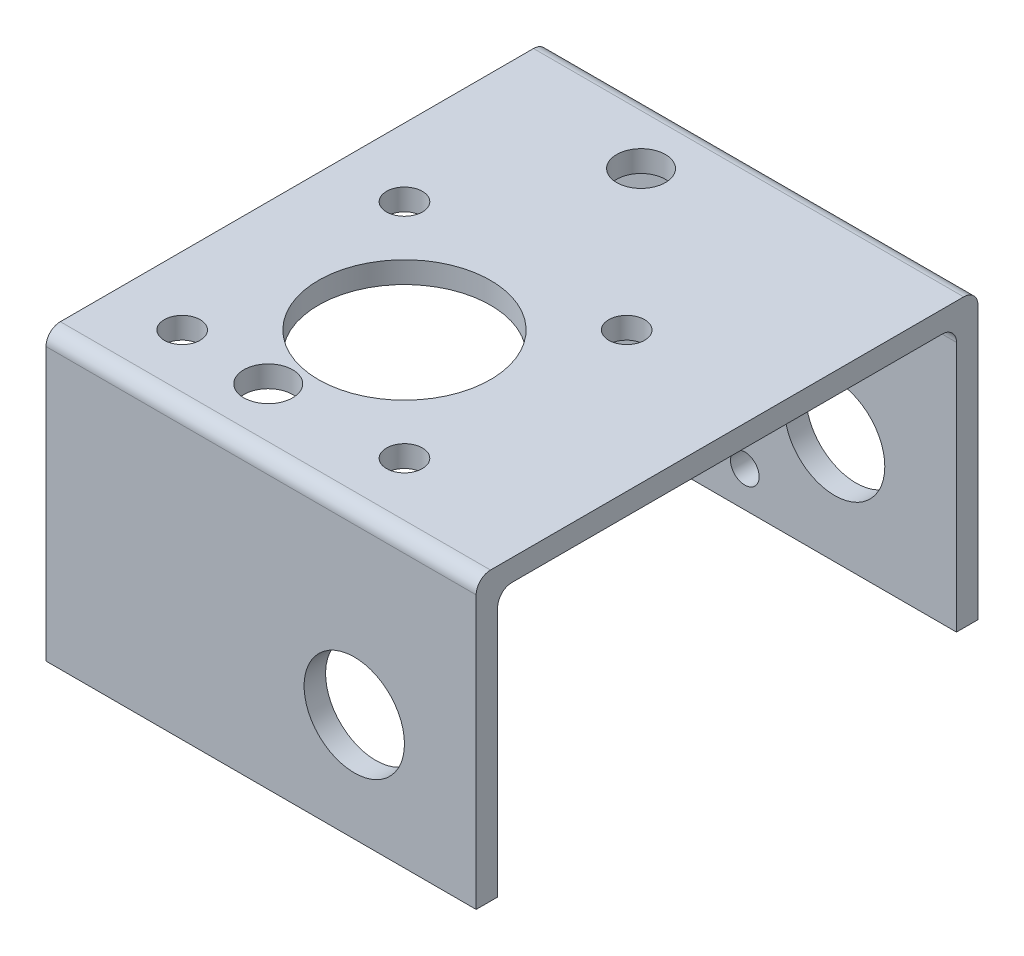
SolidWorks part; units mm, degrees
material "6061 合金"
ref_plane "前视基准面" through (0, 0, 0) normal (0, 0, 1) x (1, 0, 0)
ref_plane "上视基准面" through (0, 0, 0) normal (0, 1, 0) x (1, 0, 0)
ref_plane "右视基准面" through (0, 0, 0) normal (1, 0, 0) x (0, 0, -1)
sketch "草图1" plane through (0, 0, 0) normal (1, 0, 0) x (0, 0, -1)
  line L0 (0, 0) -> (3, 0)
  line L1 (3, 0) -> (3, 35)
  line L2 (5, 37) -> (65, 37)
  line L3 (67, 35) -> (67, 0)
  line L4 (67, 0) -> (70, 0)
  line L5 (70, 0) -> (70, 38)
  line L6 (68, 40) -> (2, 40)
  line L7 (0, 38) -> (0, 0)
  arc A0 (70, 38) -> (68, 40) centre (68, 38) ccw
  arc A1 (65, 37) -> (67, 35) centre (65, 35) cw
  arc A2 (3, 35) -> (5, 37) centre (5, 35) cw
  arc A3 (2, 40) -> (0, 38) centre (2, 38) ccw
  point P11 (70, 40)
  point P18 (0, 40)
  dimension "D6" = 2
  dimension "D1" = 3
  dimension "D2" = 3
  dimension "D3" = 3
  dimension "D4" = 70
  dimension "D5" = 40
extrude "凸台-拉伸1" add sketch "草图1" along normal blind 60
sketch "草图2" plane through (0, 40, 0) normal (0, 1, 0) x (1, 0, 0)
  line L0 (25, -19.2967) -> (25, 88.9945) construction
  line L1 (-21.8978, 25) -> (76.0197, 25) construction
  line L2 (60, 0) -> (0, 0) construction
  line L3 (0, 68) -> (0, 2) construction
  line L4 (-9.4226, 9.5) -> (65.353, 9.5) construction
  line L5 (9.5, -18.3438) -> (9.5, 73.6232) construction
  circle A0 centre (9.5, 9.5) radius 2.5
  circle A1 centre (40.5, 9.5) radius 2.5
  circle A2 centre (40.5, 40.5) radius 2.5
  circle A3 centre (9.5, 40.5) radius 2.5
  circle A4 centre (25, 25) radius 12
  dimension "D5" = 5
  dimension "D8" = 24
  dimension "D1" = 25
  dimension "D2" = 25
  dimension "D3" = 15.5
  dimension "D4" = 15.5
  dimension "D6" = 2
  dimension "D7" = 2
extrude "切除-拉伸1" cut sketch "草图2" against normal up to next
sketch "草图3" plane through (0, 0, 0) normal (0, 0, 1) x (1, 0, 0)
  line L0 (25, -15.1885) -> (25, 47.9229) construction
  line L1 (0, 38) -> (0, 0) construction
  line L2 (60, 40) -> (0, 40) construction
  circle A0 centre (43, 15) radius 7
  dimension "D1" = 14
  dimension "D2" = 25
  dimension "D3" = 18
  dimension "D4" = 25
extrude "切除-拉伸2" cut sketch "草图3" against normal through all
hole_wizard "M8 螺纹孔的螺纹孔钻头1" positions "草图4" profile "草图5" hole size "M8" standard "GB" end condition up to next
sketch "草图4" plane through (0, 40, 0) normal (0, 1, 0) x (1, 0, 0)
  line L0 (60, 70) -> (0, 70) construction
  line L1 (0, 68) -> (0, 2) construction
  line L2 (60, 35) -> (0, 35) construction
  line L3 (60, 68) -> (60, 2) construction
  point P0 (22, 61)
  point P13 (22, 9)
  dimension "D1" = 9
  dimension "D2" = 22
sketch "草图5" plane through (22, 40, -61) normal (1, 0, 0) x (0, 0, 1)
  line L0 (0, 0) -> (0, 3)
  line L1 (0, 3) -> (3.4, 3)
  line L2 (3.4, 3) -> (3.4, 0)
  line L5 (3.4, 0) -> (0, 0)
  line L11 (0, -6.35) -> (0, 107.95) construction
  dimension "通孔孔直径" = 6.8
  dimension "通孔孔深度" = 3
sketch "草图6" plane through (0, 0, -70) normal (0, 0, -1) x (-1, 0, 0)
  line L0 (-22, 38) -> (-22, -10.7821) construction
  line L1 (-60, 38) -> (0, 38) construction
  line L2 (-60, 0) -> (0, 0) construction
  line L3 (0, 0) -> (0, 38) construction
  line L4 (-22, 13.4956) -> (4.0591, 13.4956) construction
  circle A1 centre (-13.525, 5) radius 2
  circle A2 centre (-30.475, 5) radius 2
  circle A3 centre (-30.475, 21.9911) radius 2
  circle A4 centre (-13.525, 21.9911) radius 2
  circle A5 centre (-22, 13.4956) radius 12 construction
  dimension "D2" = 4
  dimension "D1" = 24
  dimension "D3" = 5
  dimension "D4" = 22
extrude "切除-拉伸3" cut sketch "草图6" against normal up to next
